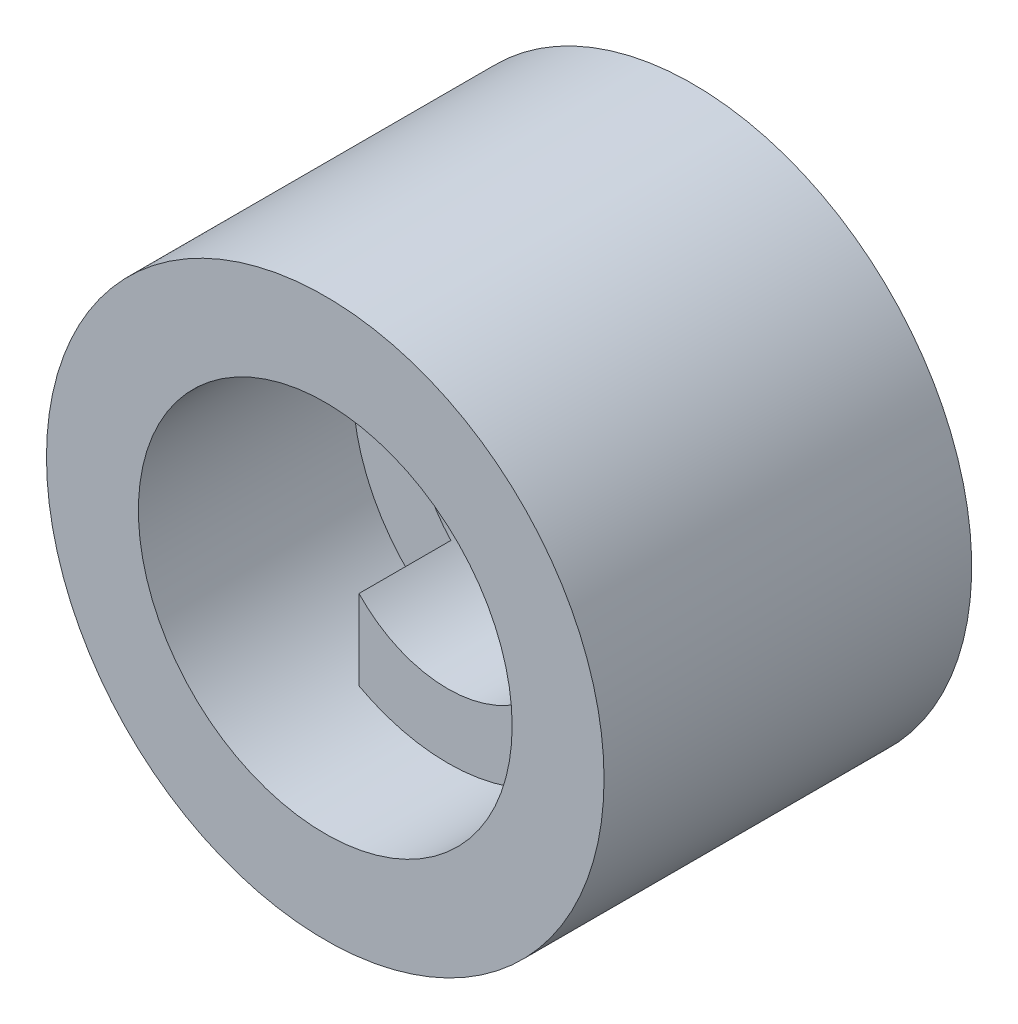
SolidWorks part; units mm, degrees
ref_plane "Alzado" through (0, 0, 0) normal (0, 0, 1) x (1, 0, 0)
ref_plane "Planta" through (0, 0, 0) normal (0, 1, 0) x (1, 0, 0)
ref_plane "Vista lateral" through (0, 0, 0) normal (1, 0, 0) x (0, 0, -1)
sketch "Croquis1" plane through (0, 0, 0) normal (0, 0, 1) x (1, 0, 0)
  circle A0 centre (0, 0) radius 6.1
  circle A1 centre (0, 0) radius 9.1
  dimension "D1" = 12.2
  dimension "D2" = 3
extrude "Saliente-Extruir1" add sketch "Croquis1" along normal blind 7
sketch "Croquis2" plane through (0, 0, 0) normal (0, 0, 1) x (1, 0, 0)
  line L0 (0, 6.1) -> (0, -6.1) construction
  line L1 (-2.9, 5.3666) -> (-2.9, -5.3666)
  line L2 (2.9, 5.3666) -> (2.9, -5.3666)
  arc A0 (-2.9, -5.3666) -> (2.9, -5.3666) centre (0, 0) ccw
  circle A1 centre (0, 0) radius 6.1 construction
  arc A2 (2.9, 5.3666) -> (-2.9, 5.3666) centre (0, 0) ccw
  dimension "D1" = 2.9
extrude "Saliente-Extruir2" add sketch "Croquis2" along normal blind 3
sketch "Croquis3" plane through (0, 0, 0) normal (0, 0, -1) x (-1, 0, 0)
  circle A0 centre (0, 0) radius 9.1
  circle A1 centre (0, 0) radius 9.1 construction
extrude "Saliente-Extruir3" add sketch "Croquis3" along normal blind 5
sketch "Croquis4" plane through (0, 0, -5) normal (0, 0, -1) x (-1, 0, 0)
  circle A0 centre (0, 0) radius 4
  dimension "D1" = 8
extrude "Cortar-Extruir1" cut sketch "Croquis4" against normal blind 23
